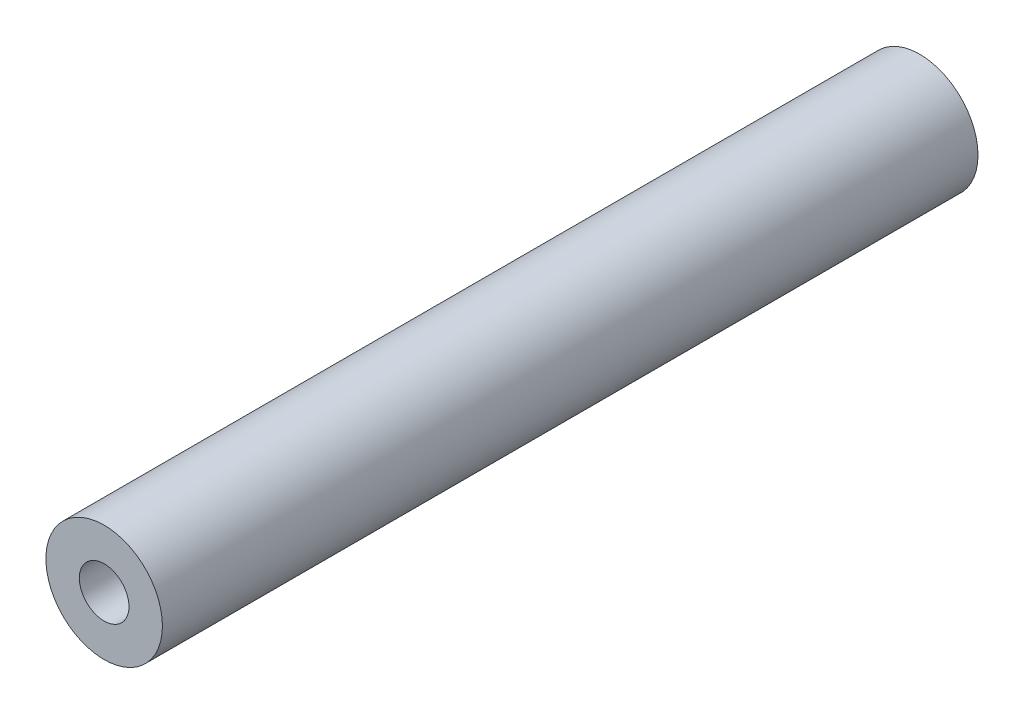
SolidWorks part; units mm, degrees
ref_plane "Front Plane" through (0, 0, 0) normal (0, 0, 1) x (1, 0, 0)
ref_plane "Top Plane" through (0, 0, 0) normal (0, 1, 0) x (1, 0, 0)
ref_plane "Right Plane" through (0, 0, 0) normal (1, 0, 0) x (0, 0, -1)
sketch "Sketch1" plane through (0, 0, 0) normal (0, 0, 1) x (1, 0, 0)
  circle A0 centre (0, 0) radius 3.175
  dimension "D1" = 6.35
extrude "Boss-Extrude1" add sketch "Sketch1" along normal blind 44.45
sketch "Sketch2" plane through (0, 0, 44.45) normal (0, 0, 1) x (1, 0, 0)
  circle A0 centre (0, 0) radius 1.778
  dimension "D1" = 3.556
hole_wizard "#6-32 Tapped Hole1" positions "Sketch3" profile "Sketch4" tap size "#6-32" standard "ANSI Inch"
sketch "Sketch3" plane through (0, 0, 44.45) normal (0, 0, 1) x (1, 0, 0)
  point P0 (0, 0)
sketch "Sketch4" plane through (0, 0, 44.45) normal (1, 0, 0) x (0, -1, 0)
  line L0 (0, 0) -> (0, 13.5127)
  line L1 (0, 13.5127) -> (1.3525, 12.7)
  line L2 (1.3525, 12.7) -> (1.3525, 0)
  line L5 (1.3525, 0) -> (0, 0)
  line L10 (0, 13.5127) -> (-1.3525, 12.7) construction
  line L11 (0, -6.35) -> (0, 107.95) construction
  dimension "Tap Drill Dia." = 2.7051
  dimension "Tap Drill Depth" = 12.7
  dimension "Drill Angle" = 118
cosmetic thread "Hole Thread1" parameters "D1"=7.112, "D2"=3.5052
ref_plane "Plane1" through (0, 0, 22.225) normal (0, 0, 1) x (1, 0, 0)
mirror "Mirror1" about plane through (0, 0, 22.225) normal (0, 0, 1) of "#6-32 Tapped Hole1"
cosmetic thread "Hole Thread2" parameters "D1"=7.112, "D2"=3.5052
